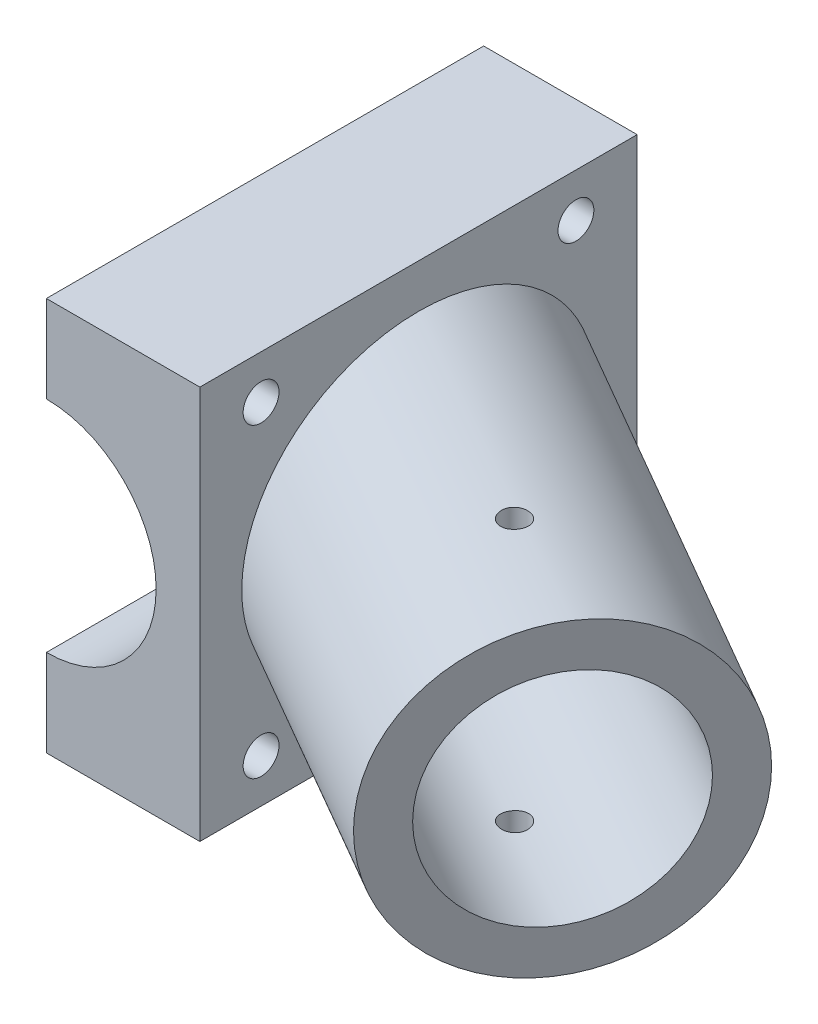
SolidWorks part; units mm, degrees
material "PLA"
ref_plane "Front Plane" through (0, 0, 0) normal (0, 0, 1) x (1, 0, 0)
ref_plane "Top Plane" through (0, 0, 0) normal (0, 1, 0) x (1, 0, 0)
ref_plane "Right Plane" through (0, 0, 0) normal (1, 0, 0) x (0, 0, -1)
sketch "Sketch1" plane through (0, 0, 0) normal (0, 0, 1) x (1, 0, 0)
  line L0 (-17.55, 22.5) -> (-17.55, 0)
  line L1 (55, 0) -> (-55, 0) construction
  line L2 (-17.55, 0) -> (17.55, 0)
  line L3 (17.55, 0) -> (17.55, 22.5)
  line L4 (-17.55, 22.5) -> (-12.55, 22.5)
  line L5 (17.55, 22.5) -> (12.55, 22.5)
  line L6 (0, -44.7868) -> (0, 44.7868) construction
  arc A0 (-12.55, 22.5) -> (12.55, 22.5) centre (0, 22.5) ccw
  dimension "D1" = 12.55
  dimension "D2" = 22.5
  dimension "D3" = 5
extrude "Boss-Extrude1" add sketch "Sketch1" along normal mid plane 50
sketch "Construct1" plane through (0, 0, 0) normal (0, 1, 0) x (1, 0, 0)
  line L0 (17.55, 0) -> (43.5308, -15) construction
  line L1 (-44.2539, 0) -> (44.2539, 0) construction
  line L2 (34.7676, -0.1782) -> (26.3131, -14.8218) construction
  line L3 (17.55, -25) -> (17.55, 25) construction
  point P6 (30.5404, -7.5)
  point P7 (30.5404, -7.5)
  dimension "D1" = 30
  dimension "D2" = 15
ref_plane "LegBuildPlane" through (26.1529, 0, 15.0994) normal (0.866, 0, 0.5) x (0.5, 0, -0.866)
sketch "Sketch5" plane through (26.1529, 0, 15.0994) normal (0.866, 0, 0.5) x (0.5, 0, -0.866)
  line L0 (-8.725, 22.5) -> (-3.775, 22.5)
  line L1 (21.325, 22.5) -> (26.275, 22.5)
  line L2 (17.2295, 0) -> (0.3205, 0) construction
  arc A0 (-3.775, 22.5) -> (21.325, 22.5) centre (8.775, 22.5) ccw
  arc A1 (-8.725, 22.5) -> (26.275, 22.5) centre (8.775, 22.5) ccw
  point P9 (8.775, 0)
  dimension "D1" = 17.5
  dimension "D2" = 12.55
  dimension "D3" = 22.5
  dimension "D4" = 0
extrude "Boss-Extrude2" add sketch "Sketch5" against normal up to surface and the other way blind 30 up to face at (17.55, 11.25, 0)
sketch "Sketch9" plane through (-17.55, 0, 0) normal (-1, 0, 0) x (0, 0, 1)
  line L0 (25, 22.5) -> (25, 0) construction
  line L1 (0.1782, 0) -> (14.8218, 0) construction
  circle A0 centre (-18, 5) radius 2.05
  circle A1 centre (18, 5) radius 2.05
  dimension "D3" = 4.1
  dimension "D1" = 7
  dimension "D2" = 36
  dimension "D4" = 5
extrude "Cut-Extrude3" cut sketch "Sketch9" against normal up to surface (35.1 mm away) up to face at (17.55, 12.0833, 0)
sketch "Construct2" plane through (0, 22.5, 0) normal (0, 1, 0) x (1, 0, 0)
  line L0 (20.1481, -15.9915) -> (32.6981, 5.7457) construction
  line L2 (50.2461, -33.3686) -> (17.55, -14.4915) construction
  line L3 (62.7961, -11.6314) -> (17.55, 14.4915) construction
  line L4 (17.55, 0) -> (26.4231, -5.1229) construction
  line L11 (-44.2539, 0) -> (44.2539, 0) construction
  dimension "D1" = 3
  dimension "D2" = 90
ref_plane "LegBuildPlane2" through (22.0356, 0, 12.7222) normal (0.866, 0, 0.5) x (0.5, 0, -0.866)
sketch "Sketch12" plane through (22.0356, 0, 12.7222) normal (0.866, 0, 0.5) x (0.5, 0, -0.866)
  line L0 (-3.775, 22.5) -> (21.325, 22.5)
  arc A0 (-3.775, 22.5) -> (21.325, 22.5) centre (8.775, 22.5) ccw
extrude "Boss-Extrude5" add sketch "Sketch12" against normal up to surface (17.4915 mm away) up to face at (17.55, 16.225, 0)
mirror "Mirror1" about plane through (17.55, 22.5, 25) normal (0, -1, 0) of "Boss-Extrude2", "Boss-Extrude1", "Cut-Extrude3", "Boss-Extrude5"
sketch "Sketch13" plane through (0, 0, 0) normal (0, 1, 0) x (1, 0, 0)
  line L0 (17.55, 0) -> (43.5308, -15) construction
  line L1 (47.7711, -37.6554) -> (65.2711, -7.3446) construction
  circle A0 centre (43.5308, -15) radius 1.55
  dimension "D2" = 3.1
  dimension "D1" = 15
extrude "Cut-Extrude4" cut sketch "Sketch13" along normal through all
sketch "Sketch16" plane through (0, 0, 0) normal (1, 0, 0) x (0, 0, -1)
  line L0 (55, 0) -> (-55, 0) construction
  line L1 (25, 45) -> (-25, 45)
  line L2 (25, 45) -> (25, 0)
  line L3 (25, 0) -> (-25, 0)
  line L4 (-25, 45) -> (-25, 0)
  line L5 (-25, 45) -> (-25, 0) construction
extrude "Cut-Extrude5" cut sketch "Sketch16" against normal up to surface (17.55 mm away) up to face at (-17.55, 40, -15.95)
equation "\"TubeDiam\"=12.55"
equation "\"D1@Sketch1\"=\"TubeDiam\""
equation "\"D2@Sketch1\"=\"ClampHeight\""
equation "\"MountLength\"=50"
equation "\"D1@Boss-Extrude1\"=\"MountLength\""
equation "\"MountHoleSize\"=3.1"
equation "\"LipWidth\"= 5"
equation "\"D3@Sketch1\"=\"LipWidth\""
equation "\"LegDiam\"=12.55"
equation "\"LegThickness\"= \"TubeDiam\" + 4.95"
equation "\"D1@Sketch5\"=\"LegThickness\""
equation "\"D2@Sketch5\"=\"TubeDiam\""
equation "\"ClampHeight\"= \"TubeDiam\" + 9.95"
equation "\"D3@Sketch5\"=\"ClampHeight\""
equation "\"HubHoleDist\"=7"
equation "\"D1@Sketch9\"=\"HubHoleDist\""
equation "\"D2@Sketch9\"=\"MountLength\"- 2 *\"HubHoleDist\""
equation "\"HubHoleSize\"=4.1"
equation "\"D3@Sketch9\"=\"HubHoleSize\""
equation "\"D2@Sketch13\"=\"MountHoleSize\""
